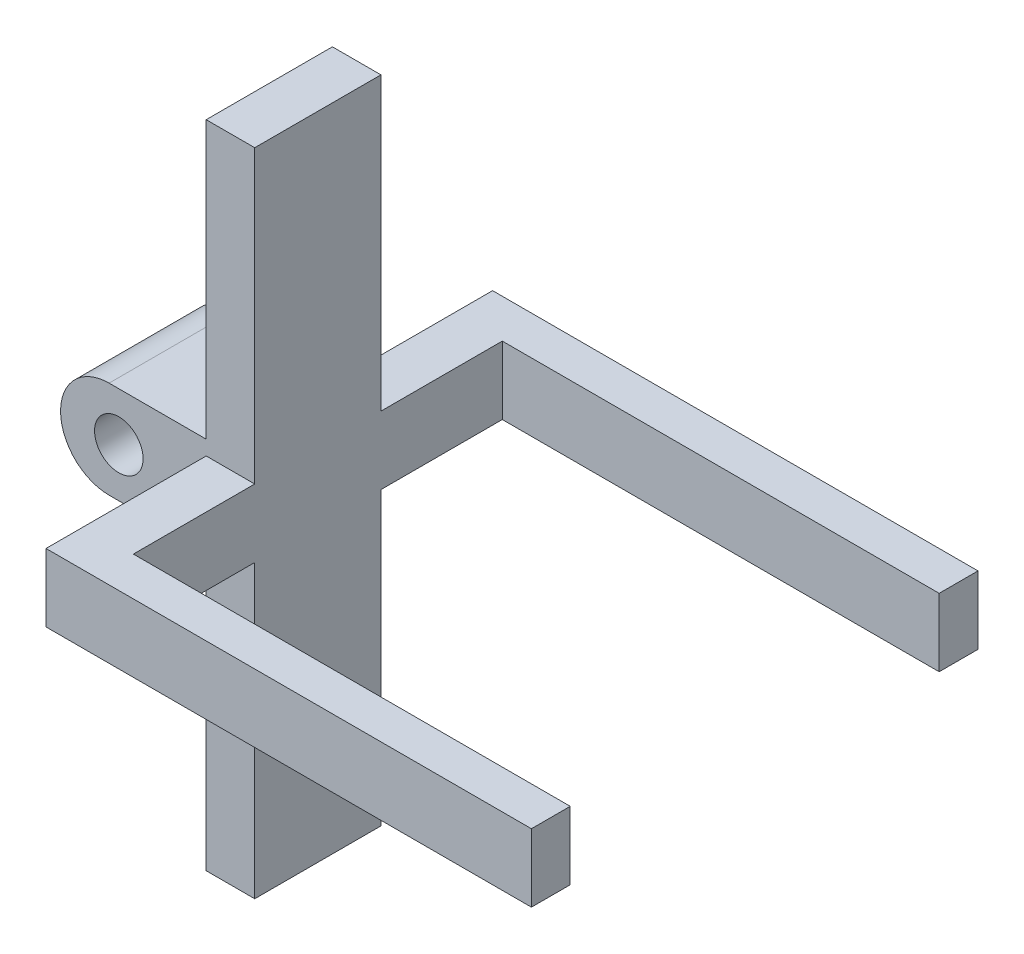
SolidWorks part; units mm, degrees
ref_plane "Front Plane" through (0, 0, 0) normal (0, 0, 1) x (1, 0, 0)
ref_plane "Top Plane" through (0, 0, 0) normal (0, 1, 0) x (1, 0, 0)
ref_plane "Right Plane" through (0, 0, 0) normal (1, 0, 0) x (0, 0, -1)
sketch "Sketch1" plane through (0, 0, 0) normal (1, 0, 0) x (0, 0, -1)
  line L1 (-6.5, -5) -> (6.5, -5)
  line L2 (-6.5, -5) -> (-6.5, 5)
  line L3 (-6.5, 5) -> (6.5, 5)
  line L4 (6.5, -5) -> (6.5, 5)
  line L5 (-6.5, -5) -> (6.5, 5) construction
  line L6 (-6.5, 5) -> (6.5, -5) construction
  point P0 (0, 0)
  dimension "D1" = 10
  dimension "D2" = 13
extrude "Boss-Extrude1" add sketch "Sketch1" along normal mid plane 15
sketch "Sketch2" plane through (0, 0, 6.5) normal (0, 0, 1) x (1, 0, 0)
  line L0 (7.15, 0) -> (-7.15, 0) construction
  line L1 (-7.5, 5) -> (-7.5, -5) construction
  circle A0 centre (-1.5, 0) radius 2.5
  dimension "D2" = 5
  dimension "D1" = 6
extrude "Cut-Extrude1" cut sketch "Sketch2" against normal blind 15
fillet "Fillet1" radius 5 2 edges at (-7.5, -5, 0) (-7.5, 5, 0)
sketch "Sketch3" plane through (7.5, 0, 0) normal (1, 0, 0) x (0, 0, -1)
  line L1 (-23, -3.5) -> (23, -3.5)
  line L2 (-23, -3.5) -> (-23, 3.5)
  line L3 (-23, 3.5) -> (23, 3.5)
  line L4 (23, -3.5) -> (23, 3.5)
  line L5 (-23, -3.5) -> (23, 3.5) construction
  line L6 (-23, 3.5) -> (23, -3.5) construction
  point P0 (0, 0)
  dimension "D1" = 7
  dimension "D2" = 46
extrude "Boss-Extrude2" add sketch "Sketch3" along normal blind 5
sketch "Sketch4" plane through (12.5, 0, 0) normal (1, 0, 0) x (0, 0, -1)
  line L0 (-23, -3.5) -> (23, -3.5) construction
  line L1 (-23, 3.5) -> (-19, 3.5)
  line L2 (-23, 3.5) -> (-23, -3.5)
  line L3 (-23, -3.5) -> (-19, -3.5)
  line L4 (-19, 3.5) -> (-19, -3.5)
  line L6 (23, 3.5) -> (19, 3.5)
  line L7 (23, 3.5) -> (23, -3.5)
  line L8 (23, -3.5) -> (19, -3.5)
  line L9 (19, 3.5) -> (19, -3.5)
  dimension "D1" = 4
extrude "Boss-Extrude3" add sketch "Sketch4" along normal blind 45
sketch "Sketch5" plane through (0, 3.5, 0) normal (0, 1, 0) x (1, 0, 0)
  line L0 (12.5, 19) -> (12.5, -19) construction
  line L1 (7.5, 6.5) -> (12.5, 6.5)
  line L2 (7.5, 6.5) -> (7.5, -6.5)
  line L3 (7.5, -6.5) -> (12.5, -6.5)
  line L4 (12.5, 6.5) -> (12.5, -6.5)
extrude "Boss-Extrude4" add sketch "Sketch5" along normal blind 30
mirror "Mirror1" about plane through (0, 0, 0) normal (0, 1, 0) of "Boss-Extrude4"
